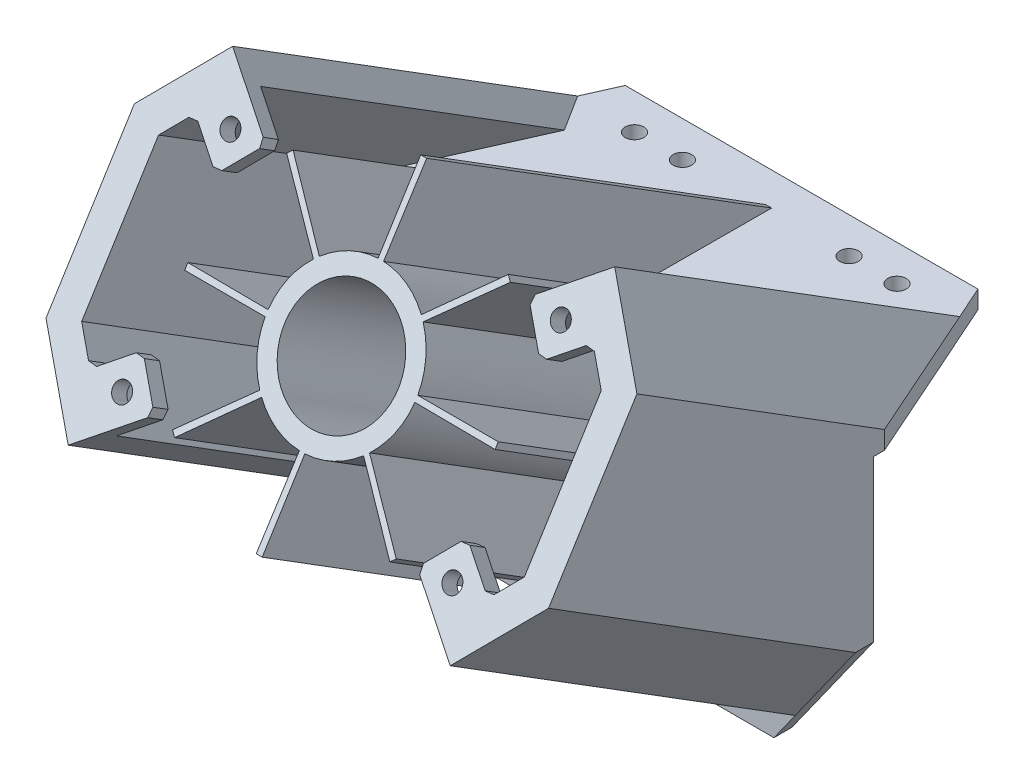
SolidWorks part; units mm, degrees
ref_plane "Front Plane" through (0, 0, 0) normal (0, 0, 1) x (1, 0, 0)
ref_plane "Top Plane" through (0, 0, 0) normal (0, 1, 0) x (1, 0, 0)
ref_plane "Right Plane" through (0, 0, 0) normal (1, 0, 0) x (0, 0, -1)
sketch "Sketch2" plane through (0, 0, 0) normal (0, 0, 1) x (1, 0, 0)
  line L0 (-110, 46) -> (-110, 49)
  line L2 (-110, 46) -> (-110, 0)
  line L3 (-110, 0) -> (-26, 0)
  line L4 (-136, 0) -> (0, 0)
  line L5 (0, 0) -> (0, 46)
  line L6 (0, 46) -> (-136, 46)
  line L7 (-136, 46) -> (-136, 0)
  line L8 (-136, 0) -> (0, 0)
  line L9 (0, 0) -> (0, 46)
  line L11 (-136, 46) -> (-136, 0)
  line L12 (-26, 46) -> (-26, 0)
  line L13 (-110, 49) -> (-26, 49)
  line L14 (-26, 49) -> (-26, 46)
  dimension "D2" = 5
  dimension "D3" = 5
  dimension "D4" = 3
  dimension "D1" = 0
extrude "Boss-Extrude1" add sketch "Sketch2" along normal blind 3 contours L13 L14 L12 L3 L2 L0
sketch "Sketch3" plane through (0, 0, 0) normal (0, 0, -1) x (-1, 0, 0)
  line L4 (0, 0) -> (136, 0)
  line L5 (0, 46) -> (0, 0)
  line L6 (136, 46) -> (0, 46)
  line L7 (136, 0) -> (136, 46)
  line L8 (0, 0) -> (136, 0)
  line L9 (0, 46) -> (0, 0)
  line L10 (136, 46) -> (0, 46)
  line L11 (136, 0) -> (136, 46)
  line M5 (110, 0) -> (110, 49)
  line M6 (110, 49) -> (26, 49)
  line M7 (26, 49) -> (26, 0)
  dimension "D1" = 0
extrude "Boss-Extrude2" add sketch "Sketch3" along normal blind 30 contours L10 M5 M6 M7 region at (-68, 47.5, 0)
sketch "Sketch4" plane through (-110, 0, 0) normal (-1, 0, 0) x (0, 0, 1)
  line L0 (3, 5) -> (-24.4943, 49)
  line L1 (3, 0) -> (3, 49) construction
  line L2 (3, 49) -> (-30, 49) construction
  dimension "D1" = 5
  dimension "D2" = 32
sketch "Sketch5" plane through (-26, 0, 0) normal (1, 0, 0) x (0, 0, -1)
  line L0 (-3, 5) -> (24.4943, 49) construction
  line L1 (-3, 5) -> (24.4943, 49)
ref_plane "Plane1" through (0, 2.7523, 4.4045) normal (0, 0.5299, 0.848) x (1, 0, 0)
sketch "Sketch6" plane through (0, 2.7523, 4.4045) normal (0, 0.5299, 0.848) x (1, 0, 0)
  line L0 (-110, 39.9646) -> (-110, -1.5898) construction
  line L1 (-110, -1.5898) -> (-26, -1.5898) construction
  line L2 (-26, -1.5898) -> (-26, 39.9646) construction
  line L3 (-26, 39.9646) -> (-26, 57.4519) construction
  line L4 (-26, 57.4519) -> (-110, 57.4519) construction
  line L5 (-110, 57.4519) -> (-110, 39.9646) construction
  line L6 (-110, 39.9646) -> (-110, -1.5898)
  line L7 (-110, -1.5898) -> (-26, -1.5898)
  line L8 (-26, -1.5898) -> (-26, 39.9646)
  line L9 (-26, 39.9646) -> (-26, 57.4519)
  line L10 (-26, 57.4519) -> (-110, 57.4519)
  line L11 (-110, 57.4519) -> (-110, 39.9646)
ref_point "Point1"
ref_point "Point2"
sketch "Sketch7" plane through (0, 2.7523, 4.4045) normal (0, 0.5299, 0.848) x (1, 0, 0)
  line L0 (-26, 2.6505) -> (-110, 2.6505)
  line L1 (-26, 54.5343) -> (-110, 54.5343)
  line L2 (-110, 42.5343) -> (-110, 14.6505)
  line L3 (-110, 42.5343) -> (-99.9308, 54.5343)
  line L4 (-110, 14.6505) -> (-99.9308, 2.6505)
  line L5 (-105, 40.7145) -> (-96.1006, 51.3204)
  line L6 (-110, 39.9646) -> (-110, -1.5898)
  line L7 (-110, -1.5898) -> (-26, -1.5898)
  line L8 (-26, -1.5898) -> (-26, 39.9646)
  line L9 (-26, 39.9646) -> (-26, 57.4519)
  line L10 (-26, 57.4519) -> (-110, 57.4519)
  line L11 (-110, 57.4519) -> (-110, 39.9646)
  line L12 (-105, 40.7145) -> (-105, 16.4703)
  line L13 (-110, -1.5898) -> (-26, -1.5898)
  line L14 (-26, -1.5898) -> (-26, 39.9646)
  line L15 (-26, 39.9646) -> (-26, 57.4519)
  line L16 (-26, 57.4519) -> (-110, 57.4519)
  line L17 (-105, 16.4703) -> (-96.1006, 5.8644)
  line L18 (-99.9308, 54.5343) -> (-96.1006, 51.3204)
  line L19 (-99.9308, 2.6505) -> (-96.1006, 5.8644)
  line L20 (-68, 54.5343) -> (-68, 2.6505) construction
  line L21 (-36.0692, 2.6505) -> (-39.8994, 5.8644)
  line L22 (-31, 16.4703) -> (-39.8994, 5.8644)
  line L23 (-26, 14.6505) -> (-36.0692, 2.6505)
  line L24 (-26, 42.5343) -> (-26, 14.6505)
  line L25 (-31, 40.7145) -> (-31, 16.4703)
  line L26 (-31, 40.7145) -> (-39.8994, 51.3204)
  line L27 (-36.0692, 54.5343) -> (-39.8994, 51.3204)
  line L28 (-26, 42.5343) -> (-36.0692, 54.5343)
  dimension "D1" = 0
  dimension "D2" = 12
  dimension "D3" = 12
  dimension "D4" = 40
  dimension "D5" = 5
extrude "Boss-Extrude3" add sketch "Sketch7" along normal blind 68 contours L4 L19 L17 L12 L5 L18 L3 L2 | L15 L28 L27 L26 L25 L22 L21 L23 L14 region at (-30.9667, 27, -10.7471) region at (-105.0333, 27, -10.7471)
sketch "Sketch8" plane through (0, 2.7523, 4.4045) normal (0, 0.5299, 0.848) x (1, 0, 0)
  line L0 (-110, -1.5898) -> (-26, -1.5898) construction
  line L1 (-26, -1.5898) -> (-26, 39.9646) construction
  line L2 (-26, 39.9646) -> (-26, 57.4519) construction
  line L3 (-26, 57.4519) -> (-110, 57.4519) construction
  line L4 (-68, 54.5343) -> (-68.5, 54.5343)
  line L6 (-110, -1.5898) -> (-26, -1.5898)
  line L7 (-26, -1.5898) -> (-26, 39.9646)
  line L8 (-39.8994, 5.8644) -> (-36.0692, 2.6505)
  line L9 (-31, 16.4703) -> (-39.8994, 5.8644)
  line L10 (-31, 40.7145) -> (-31, 16.4703)
  line L11 (-39.8994, 51.3204) -> (-31, 40.7145)
  line L12 (-36.0692, 54.5343) -> (-39.8994, 51.3204)
  line L13 (-26, 42.5343) -> (-36.0692, 54.5343)
  line L14 (-26, 14.6505) -> (-26, 42.5343)
  line L15 (-36.0692, 2.6505) -> (-26, 14.6505)
  line L16 (-39.8994, 5.8644) -> (-36.0692, 2.6505)
  line L17 (-31, 16.4703) -> (-39.8994, 5.8644)
  line L18 (-31, 40.7145) -> (-31, 16.4703)
  line L19 (-39.8994, 51.3204) -> (-31, 40.7145)
  line L20 (-36.0692, 54.5343) -> (-39.8994, 51.3204)
  line L21 (-26, 42.5343) -> (-36.0692, 54.5343)
  line L22 (-26, 14.6505) -> (-26, 42.5343)
  line L23 (-36.0692, 2.6505) -> (-26, 14.6505)
  line L24 (-105, 40.7145) -> (-96.1006, 51.3204)
  line L25 (-96.1006, 51.3204) -> (-99.9308, 54.5343)
  line L26 (-99.9308, 54.5343) -> (-110, 42.5343)
  line L27 (-110, 42.5343) -> (-110, 14.6505)
  line L28 (-110, 14.6505) -> (-99.9308, 2.6505)
  line L29 (-99.9308, 2.6505) -> (-96.1006, 5.8644)
  line L30 (-96.1006, 5.8644) -> (-105, 16.4703)
  line L31 (-105, 16.4703) -> (-105, 40.7145)
  line L32 (-105, 40.7145) -> (-96.1006, 51.3204)
  line L33 (-96.1006, 51.3204) -> (-99.9308, 54.5343)
  line L34 (-99.9308, 54.5343) -> (-110, 42.5343)
  line L35 (-110, 42.5343) -> (-110, 14.6505)
  line L36 (-110, 14.6505) -> (-99.9308, 2.6505)
  line L37 (-99.9308, 2.6505) -> (-96.1006, 5.8644)
  line L38 (-96.1006, 5.8644) -> (-105, 16.4703)
  line L39 (-105, 16.4703) -> (-105, 40.7145)
  line L40 (-26, 39.9646) -> (-26, 57.4519)
  line L41 (-26, 57.4519) -> (-110, 57.4519)
  line L42 (-110, 28.5924) -> (-26, 28.5924) construction
  line L44 (-99.9308, 54.5343) -> (-36.0692, 54.5343) construction
  line L45 (-68, 54.5343) -> (-67.5, 54.5343)
  line L46 (-68.5, 54.5343) -> (-68.5, 41.0824)
  line L48 (-67.5833, 41.0855) -> (-67.5, 54.5343)
  line L49 (-49.6563, 46.9361) -> (-49.3027, 46.5826)
  line L50 (-49.6563, 46.9361) -> (-50.0098, 47.2897)
  line L51 (-50.0098, 47.2897) -> (-59.5218, 37.7777)
  line L52 (-58.8714, 37.1317) -> (-49.3027, 46.5826)
  line L53 (-42.0581, 28.5924) -> (-42.0581, 28.0924)
  line L54 (-42.0581, 28.5924) -> (-42.0581, 29.0924)
  line L55 (-42.0581, 29.0924) -> (-55.51, 29.0924)
  line L56 (-55.5069, 28.1757) -> (-42.0581, 28.0924)
  line L57 (-49.6563, 10.2487) -> (-50.0098, 9.8951)
  line L58 (-49.6563, 10.2487) -> (-49.3027, 10.6022)
  line L59 (-49.3027, 10.6022) -> (-58.8147, 20.1142)
  line L60 (-59.4607, 19.4639) -> (-50.0098, 9.8951)
  line L61 (-68, 2.6505) -> (-68.5, 2.6505)
  line L62 (-68, 2.6505) -> (-67.5, 2.6505)
  line L63 (-67.5, 2.6505) -> (-67.5, 16.1024)
  line L64 (-68.4167, 16.0994) -> (-68.5, 2.6505)
  line L65 (-86.3437, 10.2487) -> (-86.6973, 10.6022)
  line L66 (-86.3437, 10.2487) -> (-85.9902, 9.8951)
  line L67 (-85.9902, 9.8951) -> (-76.4782, 19.4071)
  line L68 (-77.1286, 20.0531) -> (-86.6973, 10.6022)
  line L69 (-93.9419, 28.5924) -> (-93.9419, 29.0924)
  line L70 (-93.9419, 28.5924) -> (-93.9419, 28.0924)
  line L71 (-93.9419, 28.0924) -> (-80.49, 28.0924)
  line L72 (-80.4931, 29.0091) -> (-93.9419, 29.0924)
  line L73 (-86.3437, 46.9361) -> (-85.9902, 47.2897)
  line L74 (-86.3437, 46.9361) -> (-86.6973, 46.5826)
  line L75 (-86.6973, 46.5826) -> (-77.1853, 37.0706)
  line L76 (-76.5393, 37.721) -> (-85.9902, 47.2897)
  circle A0 centre (-68, 28.5924) radius 12.5
  circle A1 centre (-68, 28.5924) radius 9.5
  point P25 (-68, 28.5924)
  point P71 (-68, 28.5924)
  dimension "D3" = 25
  dimension "D4" = 3
  dimension "D5" = 0.5
  dimension "D6" = 0.5
  dimension "D7" = 8
  dimension "D1" = 0
  dimension "D2" = 0
extrude "Boss-Extrude4" add sketch "Sketch8" along normal blind 68 contours A0 A1 | A0 L52 L49 L50 L51 | A0 L48 L45 L4 L46 | A0 L76 L73 L74 L75 | A0 L72 L69 L70 L71 | A0 L68 L65 L66 L67 | A0 L64 L61 L62 L63 | A0 L60 L57 L58 L59 | A0 L56 L53 L54 L55 region at (-68.0205, 43.3817, -20.9835) region at (-68.0405, 37.3007, -17.1837) region at (-81.6737, 38.5713, -17.9777) region at (-54.3554, 38.5959, -17.9931) region at (-87.3169, 26.9826, -10.7362) region at (-48.6831, 27.0174, -10.758) region at (-81.6446, 15.4041, -3.5012) region at (-54.3263, 15.4287, -3.5166) region at (-67.9795, 10.6183, -0.5107)
sketch "Sketch9" plane through (-110, 0, 0) normal (-1, 0, 0) x (0, 0, 1)
  line L0 (0, 0) -> (0, 46)
  line L1 (0, 46) -> (-30, 46)
  line L2 (-30, 46) -> (-30, 0)
  line L3 (-30, 0) -> (0, 0)
extrude "Cut-Extrude3" cut sketch "Sketch9" against normal through all
sketch "Sketch11" plane through (0, 49, 0) normal (0, 1, 0) x (1, 0, 0)
  line L0 (-26, 1.8493) -> (-36.0692, 24.4943)
  line L1 (-36.0692, 24.4943) -> (-38.5174, 30)
  line L2 (-110, 30) -> (-26, 30) construction
  line L3 (-38.5174, 30) -> (-26, 30)
  line L4 (-26, 30) -> (-26, 1.8493)
  line L5 (-110, 1.8493) -> (-99.9308, 24.4943)
  line L6 (-99.9308, 24.4943) -> (-97.4826, 30)
  line L7 (-97.4826, 30) -> (-110, 30)
  line L8 (-110, 30) -> (-110, 1.8493)
extrude "Cut-Extrude4" cut sketch "Sketch11" against normal blind 68
sketch "Sketch12" plane through (0, 0, 3) normal (0, 0, 1) x (1, 0, 0)
  line L0 (-110, 19.1501) -> (-99.9308, 5)
  line L1 (-99.9308, 5) -> (-96.3728, 0)
  line L2 (-110, 0) -> (-26, 0) construction
  line L3 (-96.3728, 0) -> (-110, 0)
  line L4 (-110, 0) -> (-110, 19.1501)
  line L5 (-26, 19.1501) -> (-36.0692, 5)
  line L6 (-36.0692, 5) -> (-39.6272, 0)
  line L7 (-39.6272, 0) -> (-26, 0)
  line L8 (-26, 0) -> (-26, 19.1501)
extrude "Cut-Extrude5" cut sketch "Sketch12" against normal blind 68
sketch "Sketch13" plane through (-81.6645, 58.1122, -36.3125) normal (0.766, -0.5451, 0.3406) x (0.2775, -0.1975, -0.9402)
  line L0 (-75.7166, 11.3449) -> (-73.0106, 10.0496)
  line L1 (-75.7166, 11.3449) -> (-19.0207, -15.7942) construction
  line L2 (-73.0106, 10.0496) -> (-76.4647, 2.8337)
  line L3 (-76.4647, 2.8337) -> (-79.1707, 4.129)
  line L4 (-81.6944, -1.1432) -> (-75.7166, 11.3449) construction
  line L5 (-79.1707, 4.129) -> (-75.7166, 11.3449)
  dimension "D1" = 3
  dimension "D2" = 8
extrude "Boss-Extrude5" add sketch "Sketch13" along normal blind 8
chamfer "Chamfer1" distance 1 angle 45 3 edges at (-101.2429, 76.3169, 36.8516) (-95.1145, 71.956, 39.5766) (-89.9722, 77.1531, 36.3291)
sketch "Sketch14" plane through (-53.5065, -38.075, 23.7919) normal (0.766, 0.5451, -0.3406) x (-0.2775, -0.1975, -0.9402)
  line L0 (-37.4093, 91.3722) -> (-34.7034, 90.0769)
  line L1 (-37.4093, 91.3722) -> (22.1144, 62.8795) construction
  line L2 (-34.7034, 90.0769) -> (-31.2493, 97.2928)
  line L3 (-31.2493, 97.2928) -> (-33.9552, 98.5881)
  line L4 (-31.4316, 103.8602) -> (-37.4093, 91.3722) construction
  line L5 (-37.4093, 91.3722) -> (-33.9552, 98.5881)
  dimension "D1" = 3
  dimension "D2" = 8
extrude "Boss-Extrude6" add sketch "Sketch14" along normal blind 8
chamfer "Chamfer2" distance 1 angle 45 3 edges at (-89.9722, 47.3261, 54.9671) (-95.1145, 52.5233, 51.7195) (-101.2429, 48.1623, 54.4445)
sketch "Sketch15" plane through (1.8564, 1.321, -0.8255) normal (-0.766, -0.5451, 0.3406) x (0.2775, 0.1975, 0.9402)
  line L0 (37.9724, 90.1959) -> (35.2664, 88.9006)
  line L1 (37.9724, 90.1959) -> (-18.7235, 63.0568) construction
  line L2 (35.2664, 88.9006) -> (38.7205, 81.6847)
  line L3 (38.7205, 81.6847) -> (41.4265, 82.98)
  line L4 (43.9502, 77.7078) -> (37.9724, 90.1959) construction
  line L5 (41.4265, 82.98) -> (37.9724, 90.1959)
  dimension "D1" = 8
  dimension "D2" = 3
extrude "Boss-Extrude7" add sketch "Sketch15" along normal blind 8
chamfer "Chamfer3" distance 1 angle 45 3 edges at (-34.7571, 76.3169, 36.8516) (-40.8855, 71.956, 39.5766) (-46.0278, 77.1531, 36.3291)
sketch "Sketch16" plane through (-26.3016, 18.7161, -11.6951) normal (-0.766, 0.5451, -0.3406) x (-0.2775, 0.1975, 0.9402)
  line L0 (75.1535, 12.5212) -> (72.4476, 11.2259)
  line L1 (75.1535, 12.5212) -> (15.6298, -15.9715) construction
  line L2 (72.4476, 11.2259) -> (68.9935, 18.4418)
  line L3 (68.9935, 18.4418) -> (71.6994, 19.7371)
  line L4 (69.1758, 25.0092) -> (75.1535, 12.5212) construction
  line L5 (71.6994, 19.7371) -> (75.1535, 12.5212)
  dimension "D1" = 8
  dimension "D2" = 3
extrude "Boss-Extrude8" add sketch "Sketch16" along normal blind 8
chamfer "Chamfer4" distance 1 angle 45 3 edges at (-34.7571, 48.1623, 54.4445) (-46.0278, 47.3261, 54.9671) (-40.8855, 52.5233, 51.7195)
sketch "Sketch17" plane through (0, 38.7868, 62.0718) normal (0, 0.5299, 0.848) x (1, 0, 0)
  circle A0 centre (-95.6076, 45.6851) radius 1.55
  circle A1 centre (-95.6076, 11.4997) radius 1.55
  circle A2 centre (-40.3924, 45.6851) radius 1.55
  circle A3 centre (-40.3924, 11.4997) radius 1.55
  point P0 (-95.6076, 45.6851)
  point P1 (-95.6076, 11.4997)
  point P2 (-40.3924, 11.4997)
  point P3 (-40.3924, 45.6851)
  dimension "D1" = 3.1
  dimension "D2" = 3.1
  dimension "D3" = 3.1
  dimension "D4" = 3.1
extrude "Cut-Extrude6" cut sketch "Sketch17" against normal up to next
sketch "Sketch18" plane through (0, 49, 0) normal (0, 1, 0) x (1, 0, 0)
  line L0 (-97.4826, 30) -> (-38.5174, 30) construction
  line L1 (-68, 30) -> (-68, 26.0807) construction
  circle A0 centre (-89.9308, 24) radius 1.55
  circle A1 centre (-81.9308, 24) radius 1.55
  circle A2 centre (-54.0692, 24) radius 1.55
  circle A3 centre (-46.0692, 24) radius 1.55
  point P7 (-68, 30)
  dimension "D1" = 10
  dimension "D3" = 3.1
  dimension "D4" = 3.1
  dimension "D2" = 6
  dimension "D5" = 8
extrude "Cut-Extrude7" cut sketch "Sketch18" against normal up to next
sketch "Sketch19" plane through (0, 0, 3) normal (0, 0, 1) x (1, 0, 0)
  line L0 (-88.3808, 49) -> (-91.4808, 49) construction
  line L1 (-80.3808, 49) -> (-83.4808, 49) construction
  line L4 (-88.3808, 49) -> (-91.4808, 49)
  line L5 (-80.3808, 49) -> (-83.4808, 49)
  line L6 (-68, 0) -> (-68, 3.332) construction
  line L8 (-89.9308, 49) -> (-89.9308, 0) construction
  line L9 (-96.3728, 0) -> (-39.6272, 0) construction
  line L10 (-81.9308, 49) -> (-81.9308, 0) construction
  circle A0 centre (-89.9308, 8) radius 1.55
  circle A2 centre (-46.0692, 8) radius 1.55
  dimension "D1" = 8
sketch "Sketch20" plane through (0, 0, 3) normal (0, 0, 1) x (1, 0, 0)
  line L0 (-68, 0) -> (-68, 9.4152) construction
  line L1 (-96.3728, 0) -> (-39.6272, 0) construction
ref_axis "Axis1" through (-68, 0, 3) along (0, 1, 0)
ref_plane "Plane2" through (-68, 0, 0) normal (1, 0, 0) x (0, 0, -1)
sketch "Sketch21" plane through (0, 0, 3) normal (0, 0, 1) x (1, 0, 0)
  line L0 (-45.5, 18.45) -> (-90.5, 18.45)
  line L1 (-90.5, 18.45) -> (-90.5, -3.55)
  line L2 (-90.5, -3.55) -> (-45.5, -3.55)
  line L3 (-45.5, -3.55) -> (-45.5, 18.45)
  line L4 (-89.5, -2.55) -> (-46.5, -2.55)
  line L5 (-46.5, -2.55) -> (-46.5, 17.45)
  line L6 (-46.5, 17.45) -> (-89.5, 17.45)
  line L7 (-89.5, 17.45) -> (-89.5, -2.55)
  line L8 (-89.5, -2.55) -> (-46.5, -2.55)
  line L9 (-46.5, -2.55) -> (-46.5, 17.45)
  line L10 (-46.5, 17.45) -> (-89.5, 17.45)
  line L11 (-89.5, 17.45) -> (-89.5, -2.55)
  dimension "D1" = 0
  dimension "D2" = 1
extrude "Cut-Extrude8" cut sketch "Sketch21" along normal through all contours L0 L1 L2 L3
sketch "Sketch22" plane through (0, 0, 3) normal (0, 0, 1) x (1, 0, 0)
  circle A1 centre (-48, -1.05) radius 1.05
  circle A2 centre (-48, -1.05) radius 1.05
  circle A3 centre (-88, -1.05) radius 1.05
  circle A4 centre (-88, -1.05) radius 1.05
  circle A5 centre (-88, 15.95) radius 1.05
  circle A6 centre (-88, 15.95) radius 1.05
  circle A7 centre (-48, 15.95) radius 1.05
  circle A8 centre (-48, 15.95) radius 1.05
  dimension "D1" = 0
  dimension "D2" = 0
  dimension "D3" = 0
  dimension "D4" = 0
extrude "Cut-Extrude9" cut sketch "Sketch22" against normal up to surface (3 mm away) up to face at (-75, 26.1917, 0)
